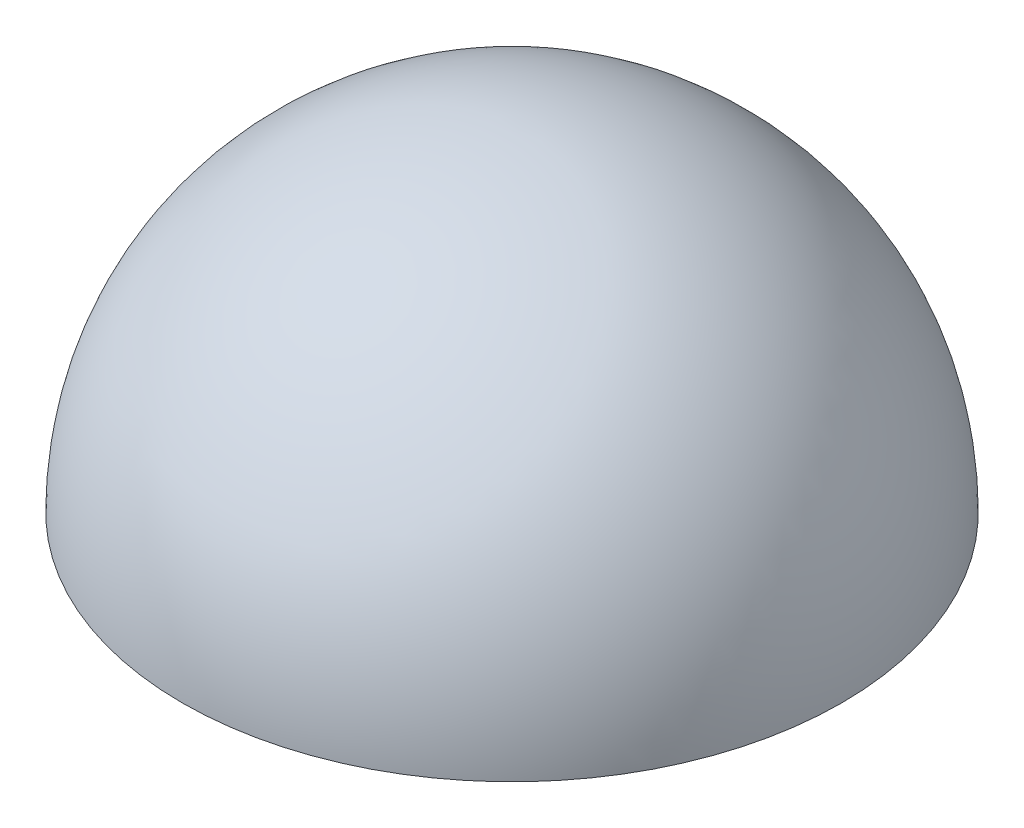
SolidWorks part; units mm, degrees
ref_plane "Front Plane" through (0, 0, 0) normal (0, 0, 1) x (1, 0, 0)
ref_plane "Top Plane" through (0, 0, 0) normal (0, 1, 0) x (1, 0, 0)
ref_plane "Right Plane" through (0, 0, 0) normal (1, 0, 0) x (0, 0, -1)
sketch "Sketch1" plane through (0, 0, 0) normal (0, 0, 1) x (1, 0, 0)
  line L0 (-14.4, 0) -> (14.4, 0)
  line L1 (0, -1000) -> (0, 49000) construction
  arc A0 (14.4, 0) -> (-14.4, 0) centre (0, 0) ccw
  dimension "D1" = 14.4
revolve "Revolve1" add sketch "Sketch1" angle 360 about L1 region at (-6.1115, 6.1115, 0)
sketch "Sketch2" plane through (0, 0, 0) normal (0, -1, 0) x (1, 0, 0)
  line L1 (4.8786, -8.45) -> (9.7572, 0)
  line L2 (9.7572, 0) -> (4.8786, 8.45)
  line L3 (4.8786, 8.45) -> (-4.8786, 8.45)
  line L4 (-4.8786, 8.45) -> (-9.7572, 0)
  line L5 (-9.7572, 0) -> (-4.8786, -8.45)
  line L6 (-4.8786, -8.45) -> (4.8786, -8.45)
  circle A0 centre (0, 0) radius 8.45 construction
  dimension "D1" = 16.9
extrude "Cut-Extrude2" cut sketch "Sketch2" against normal blind 3.5
sketch "Sketch3" plane through (0, 3.5, 0) normal (0, -1, 0) x (1, 0, 0)
  line L0 (-4.8786, 8.45) -> (-9.7572, 0) construction
  line L1 (3.7239, -6.45) -> (7.4478, 0)
  line L2 (7.4478, 0) -> (3.7239, 6.45)
  line L3 (3.7239, 6.45) -> (-3.7239, 6.45)
  line L4 (-3.7239, 6.45) -> (-7.4478, 0)
  line L5 (-7.4478, 0) -> (-3.7239, -6.45)
  line L6 (-3.7239, -6.45) -> (3.7239, -6.45)
  circle A0 centre (0, 0) radius 5.1
  circle A1 centre (0, 0) radius 6.45 construction
  dimension "D1" = 10.2
  dimension "D2" = 2
extrude "Cut-Extrude4" cut sketch "Sketch3" against normal blind 2 contours L3 L4 L5 L6 L1 L2
sketch "Sketch4" plane through (0, 0, 0) normal (1, 0, 0) x (0, 0, -1)
  line L0 (-6.45, 5.5) -> (0, 5.5)
  line L1 (0, 5.5) -> (0, 13.5)
  line L2 (0, 5.5) -> (-6.45, 5.5) construction
  ellipse E0 centre (0, 5.5) end of major axis (0, 13.5) minor radius 6.45 (0, 13.5) -> (-6.45, 5.5) ccw
  dimension "D1" = 8
revolve "Cut-Revolve1" cut sketch "Sketch4" angle 360 about L1
sketch "Sketch7" plane through (0, 0, 0) normal (0, -1, 0) x (1, 0, 0)
  line L0 (861.1657, -497.1943) -> (-42197.1217, 24362.5196) construction
  line L1 (-861.1657, -497.1943) -> (42197.1217, 24362.5196) construction
  line L2 (0, 0) -> (0, -49719.4277) construction
  circle A0 centre (-9.5263, 5.5) radius 1
  circle A1 centre (9.5263, 5.5) radius 1
  circle A2 centre (0, -11) radius 1
  point P16 (0, 0)
  dimension "D1" = 2
  dimension "D3" = 3
  dimension "D2" = 11
  dimension "D4" = 60
  dimension "D5" = 60
extrude "Cut-Extrude6" cut sketch "Sketch7" against normal blind 7
sketch "Sketch8" plane through (0, 0, 0) normal (0, -1, 0) x (1, 0, 0)
  line L1 (-8.4004, 3.55) -> (-7.2746, 5.5)
  line L2 (-7.2746, 5.5) -> (-8.4004, 7.45)
  line L3 (-8.4004, 7.45) -> (-10.6521, 7.45)
  line L4 (-10.6521, 7.45) -> (-11.7779, 5.5)
  line L5 (-11.7779, 5.5) -> (-10.6521, 3.55)
  line L6 (-10.6521, 3.55) -> (-8.4004, 3.55)
  line L24 (7.2746, 5.5) -> (8.4004, 3.55)
  line L25 (8.4004, 3.55) -> (10.6521, 3.55)
  line L26 (10.6521, 3.55) -> (11.7779, 5.5)
  line L27 (11.7779, 5.5) -> (10.6521, 7.45)
  line L28 (10.6521, 7.45) -> (8.4004, 7.45)
  line L29 (8.4004, 7.45) -> (7.2746, 5.5)
  line L30 (1.1258, -9.05) -> (-1.1258, -9.05)
  line L31 (-1.1258, -9.05) -> (-2.2517, -11)
  line L32 (-2.2517, -11) -> (-1.1258, -12.95)
  line L33 (-1.1258, -12.95) -> (1.1258, -12.95)
  line L34 (1.1258, -12.95) -> (2.2517, -11)
  line L35 (2.2517, -11) -> (1.1258, -9.05)
  circle A0 centre (-9.5263, 5.5) radius 1.95 construction
  circle A1 centre (9.5263, 5.5) radius 1.95 construction
  circle A2 centre (0, -11) radius 1.95 construction
  point P27 (0, 0)
  dimension "D1" = 3.9
  dimension "D2" = 3
extrude "Cut-Extrude7" cut sketch "Sketch8" against normal blind 2.2
sketch "Sketch9" plane through (0, 3.5, 0) normal (0, -1, 0) x (1, 0, 0)
  line L0 (-4.8786, -8.45) -> (4.8786, -8.45) construction
  line L1 (4.9363, -8.55) -> (9.8727, 0)
  line L2 (9.8727, 0) -> (4.9363, 8.55)
  line L3 (4.9363, 8.55) -> (-4.9363, 8.55)
  line L4 (-4.9363, 8.55) -> (-9.8727, 0)
  line L5 (-9.8727, 0) -> (-4.9363, -8.55)
  line L6 (-4.9363, -8.55) -> (4.9363, -8.55)
  circle A0 centre (0, 0) radius 8.55 construction
  dimension "D1" = 0.1
extrude "Cut-Extrude8" cut sketch "Sketch9" against normal blind 2 and the other way blind 12
